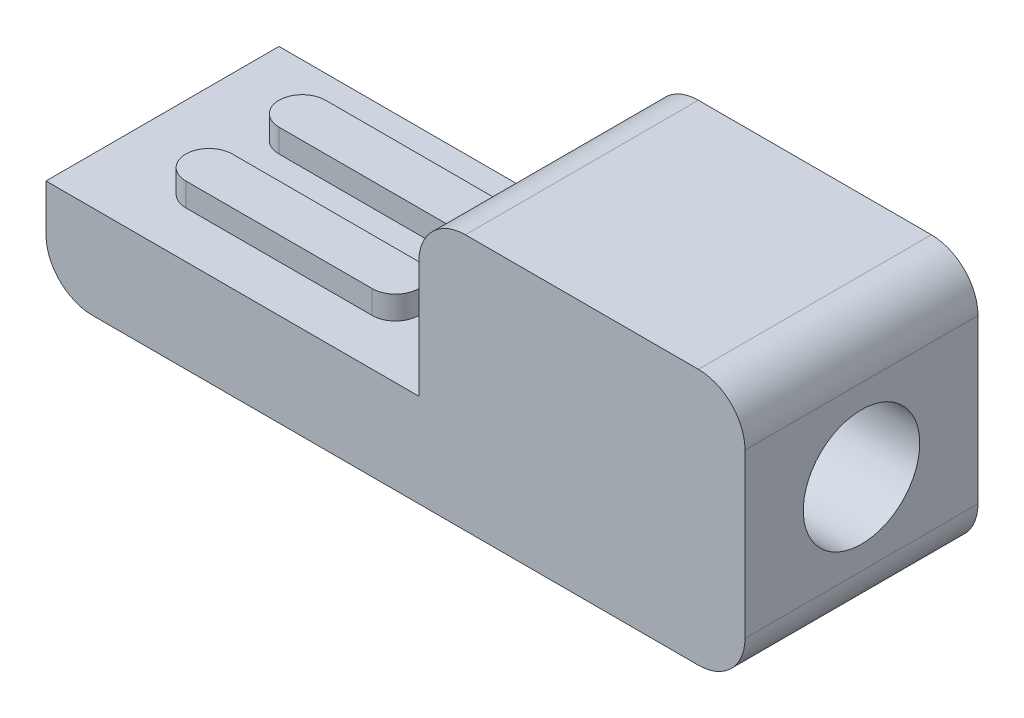
SolidWorks part; units mm, degrees
material "6061-O (SS)"
ref_plane "정면" through (0, 0, 0) normal (0, 0, 1) x (1, 0, 0)
ref_plane "윗면" through (0, 0, 0) normal (0, 1, 0) x (1, 0, 0)
ref_plane "우측면" through (0, 0, 0) normal (1, 0, 0) x (0, 0, -1)
sketch "스케치1" plane through (0, 0, 0) normal (0, 0, 1) x (1, 0, 0)
  line L0 (0, 0) -> (-15, 0)
  line L3 (-15, 0) -> (-15, 2)
  line L4 (-15, 2) -> (-7, 2)
  line L5 (-7, 2) -> (-7, 5.5)
  line L6 (-7, 5.5) -> (0, 5.5)
  line L7 (0, 5.5) -> (0, 0)
  dimension "D1" = 5.5
  dimension "D4" = 2
  dimension "D5" = 7
  dimension "D6" = 15
extrude "보스-돌출1" add sketch "스케치1" along normal mid plane 5
fillet "필렛1" radius 1 4 edges at (-7, 5.5, 0) (0, 0, 0) (0, 5.5, 0) (-15, 0, 0)
hole_wizard "M3 나사 구멍1" positions "스케치2" profile "스케치3" tap size "M3" standard "KS"
sketch "스케치2" plane through (0, 0, 0) normal (1, 0, 0) x (0, 0, -1)
  line L0 (-2.5, 1) -> (-2.5, 4.5) construction
  point P0 (0, 2.75)
  point P8 (-2.5, 2.75)
sketch "스케치3" plane through (0, 2.75, 0) normal (0, 1, 0) x (0, 0, -1)
  line L0 (0, 0) -> (0, 5.7511)
  line L1 (0, 5.7511) -> (1.25, 5)
  line L2 (1.25, 5) -> (1.25, 0)
  line L5 (1.25, 0) -> (0, 0)
  line L10 (0, 5.7511) -> (-1.25, 5) construction
  line L11 (0, -6.35) -> (0, 107.95) construction
  dimension "탭 드릴 지름" = 2.5
  dimension "탭 드릴 깊이" = 5
  dimension "드릴 각도" = 118
cosmetic thread "구멍 나사산1" parameters "D1"=4, "D2"=3
sketch "스케치4" plane through (0, 2, 0) normal (0, 1, 0) x (1, 0, 0)
  line L0 (-13, 1) -> (-9, 1) construction
  line L1 (-13, 1.5) -> (-9, 1.5)
  line L2 (-13, 0.5) -> (-9, 0.5)
  line L3 (-15, 0) -> (-7, 0) construction
  line L6 (-15, -2.5) -> (-15, 2.5) construction
  line L8 (-7, -2.5) -> (-7, 2.5) construction
  line L9 (-13, -1) -> (-9, -1) construction
  line L10 (-13, -1.5) -> (-9, -1.5)
  line L11 (-13, -0.5) -> (-9, -0.5)
  arc A0 (-13, 1.5) -> (-13, 0.5) centre (-13, 1) ccw
  arc A1 (-9, 0.5) -> (-9, 1.5) centre (-9, 1) ccw
  arc A2 (-13, -1.5) -> (-13, -0.5) centre (-13, -1) cw
  arc A3 (-9, -0.5) -> (-9, -1.5) centre (-9, -1) cw
  point P2 (-11, 1)
  point P18 (-11, -1)
  point P26 (-11, 0)
  dimension "D1" = 1
  dimension "D2" = 4
  dimension "D3" = 1
extrude "보스-돌출2" add sketch "스케치4" along normal blind 0.5
